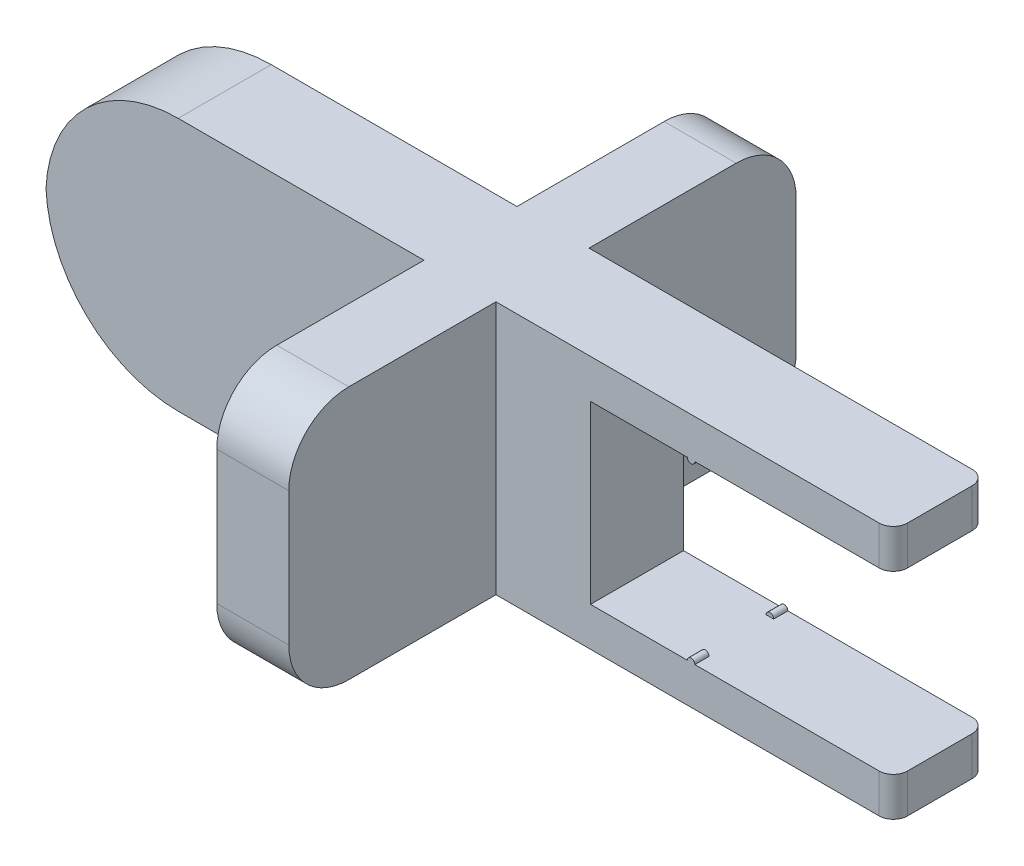
SolidWorks part; units mm, degrees
ref_plane "Front Plane" through (0, 0, 0) normal (0, 0, 1) x (1, 0, 0)
ref_plane "Top Plane" through (0, 0, 0) normal (0, 1, 0) x (1, 0, 0)
ref_plane "Right Plane" through (0, 0, 0) normal (1, 0, 0) x (0, 0, -1)
sketch "Sketch1" plane through (0, 0, 0) normal (0, 0, 1) x (1, 0, 0)
  line L0 (0, -6.71) -> (0, 6.71)
  line L1 (0, 6.71) -> (21.02, 6.71)
  line L2 (21.02, 6.71) -> (21.02, 4.65)
  line L4 (5, 4.65) -> (5, -4.65)
  line L6 (21.02, -4.65) -> (21.02, -6.71)
  line L7 (21.02, -6.71) -> (0, -6.71)
  line L8 (10.52, 4.65) -> (21.02, 4.65)
  line L9 (5, 4.65) -> (10.12, 4.65)
  line L10 (5, -4.65) -> (10.12, -4.65)
  line L11 (10.52, -4.65) -> (21.02, -4.65)
  arc A0 (10.52, 4.65) -> (10.12, 4.65) centre (10.32, 4.65) cw
  arc A1 (10.12, -4.65) -> (10.52, -4.65) centre (10.32, -4.65) cw
  point P4 (0, 0)
  point P17 (10.32, 4.45)
  point P18 (9.9351, 4.7638)
  point P19 (0, 0)
  point P20 (0, 0)
  point P21 (8.319, -4.65)
  point P22 (10.177, 4.65)
  point P23 (10.0956, 4.6622)
  dimension "D6" = 2.26
  dimension "D1" = 13.42
  dimension "D2" = 2.06
  dimension "D3" = 16.02
  dimension "D4" = 5
  dimension "D5" = 10.5
extrude "Boss-Extrude1" add sketch "Sketch1" along normal blind 4.92 contours L0 L1 L2 L8 A0 L9 L4 L10 A1 L11 L6 L7
sketch "Sketch2" plane through (0, 6.71, 0) normal (0, 1, 0) x (1, 0, 0)
  line L0 (18.6177, -4.92) -> (20.27, -4.92)
  line L1 (0, -4.92) -> (21.02, -4.92) construction
  line L2 (21.02, -4.17) -> (21.02, -0.75)
  line L3 (20.27, 0) -> (18.6177, 0)
  line L4 (0, 0) -> (21.02, 0) construction
  line L5 (18.6177, 0) -> (18.6177, 2.6631)
  line L6 (18.6177, 2.6631) -> (23.7844, 2.6631)
  line L7 (23.7844, 2.6631) -> (23.7844, -9.5322)
  line L8 (23.7844, -9.5322) -> (18.6177, -9.5322)
  line L9 (18.6177, -9.5322) -> (18.6177, -4.92)
  arc A0 (20.27, -4.92) -> (21.02, -4.17) centre (20.27, -4.17) ccw
  arc A1 (21.02, -0.75) -> (20.27, 0) centre (20.27, -0.75) ccw
  point P16 (21.02, -4.92)
  point P19 (21.02, 0)
  dimension "D1" = 0.75
extrude "Cut-Extrude1" cut sketch "Sketch2" against normal up to surface (13.42 mm away) up to face at (10.51, -6.71, 2.46)
sketch "Sketch3" plane through (21.02, 0, 0) normal (1, 0, 0) x (0, 0, -1)
  line L1 (-4.17, 4.65) -> (-0.75, 4.65)
  line L2 (-4.17, 4.65) -> (-4.17, -4.65)
  line L3 (-4.17, -4.65) -> (-0.75, -4.65)
  line L4 (-0.75, 4.65) -> (-0.75, -4.65)
extrude "Cut-Extrude2" cut sketch "Sketch3" against normal up to surface (16.02 mm away) up to face at (5, 0, 2.46)
sketch "Sketch4" plane through (0, 0, 0) normal (-1, 0, 0) x (0, 0, 1)
  line L0 (2.46, 6.71) -> (2.46, -6.71) construction
  line L1 (4.92, 6.71) -> (0, 6.71) construction
  line L2 (4.92, -6.71) -> (0, -6.71) construction
  line L4 (12.705, -6.71) -> (-7.785, -6.71)
  line L5 (15.88, -3.535) -> (15.88, 3.535)
  line L6 (12.705, 6.71) -> (-7.785, 6.71)
  line L7 (-10.96, -3.535) -> (-10.96, 3.535)
  line L8 (15.88, -6.71) -> (-10.96, 6.71) construction
  line L9 (15.88, 6.71) -> (-10.96, -6.71) construction
  arc A0 (-7.785, 6.71) -> (-10.96, 3.535) centre (-7.785, 3.535) ccw
  arc A1 (-7.785, -6.71) -> (-10.96, -3.535) centre (-7.785, -3.535) cw
  arc A2 (12.705, -6.71) -> (15.88, -3.535) centre (12.705, -3.535) ccw
  arc A3 (15.88, 3.535) -> (12.705, 6.71) centre (12.705, 3.535) ccw
  point P6 (2.46, 0)
  dimension "D3" = 3.175
  dimension "D1" = 13.42
  dimension "D2" = 26.84
extrude "Boss-Extrude2" add sketch "Sketch4" along normal blind 3.81
sketch "Sketch5" plane through (-3.81, 0, 0) normal (-1, 0, 0) x (0, 0, 1)
  line L0 (0, 6.71) -> (4.92, 6.71)
  line L1 (4.92, 6.71) -> (4.92, -6.71)
  line L2 (4.92, -6.71) -> (0, -6.71)
  line L3 (0, -6.71) -> (0, 6.71)
extrude "Boss-Extrude3" add sketch "Sketch5" along normal blind 20
fillet "Fillet1" radius 7 2 edges at (-23.81, -6.71, 2.46) (-23.81, 6.71, 2.46)
